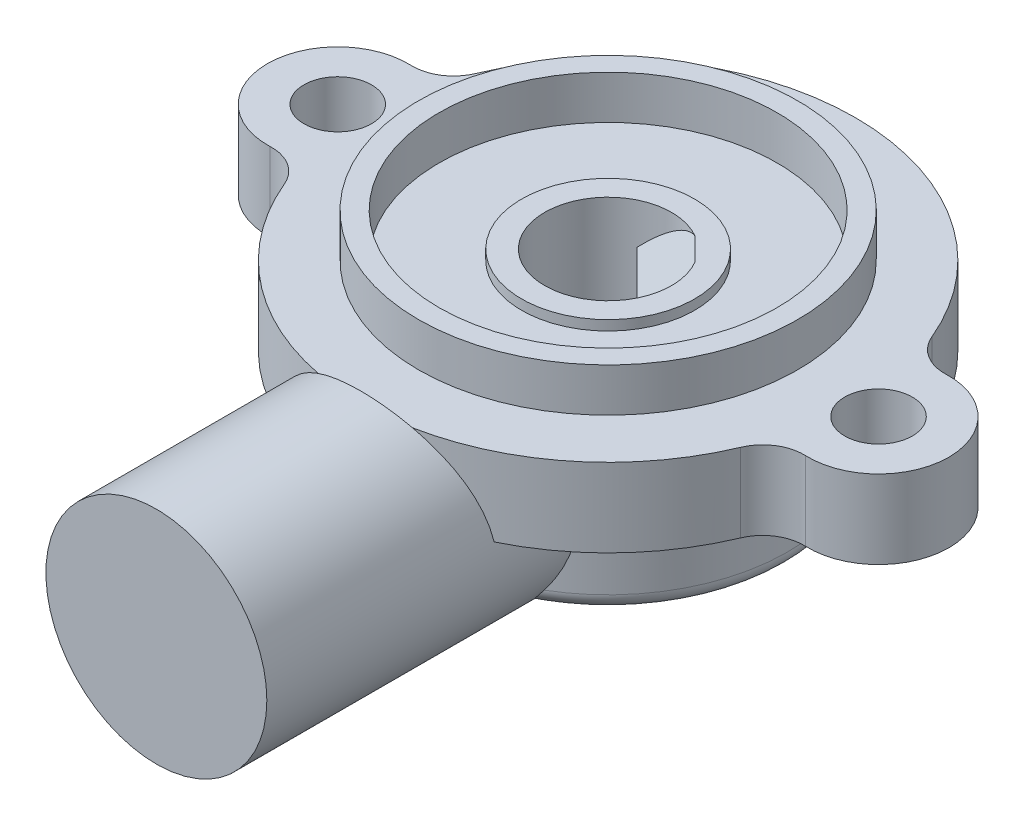
SolidWorks part; units mm, degrees
ref_plane "Front Plane" through (0, 0, 0) normal (0, 0, 1) x (1, 0, 0)
ref_plane "Top Plane" through (0, 0, 0) normal (0, 1, 0) x (1, 0, 0)
ref_plane "Right Plane" through (0, 0, 0) normal (1, 0, 0) x (0, 0, -1)
sketch "Sketch2" plane through (0, 0, 0) normal (0, 1, 0) x (1, 0, 0)
  line L0 (-20.828, 0) -> (20.828, 0) construction
  line L1 (-2.1716, 4.3808) -> (4.3808, -2.1716)
  line L2 (1.1046, 1.1046) -> (-3.4574, -3.4574) construction
  line L3 (-26.2509, 0) -> (-20.828, 0) construction
  line L4 (20.828, 0) -> (26.2509, 0) construction
  arc A0 (-18.4199, -4.8589) -> (18.4199, -4.8589) centre (0, 0) ccw
  circle A1 centre (-20.828, 0) radius 2.6035
  circle A2 centre (20.828, 0) radius 2.6035
  circle A3 centre (0, 0) radius 14.605
  circle A4 centre (0, 0) radius 13.0175
  circle A5 centre (0, 0) radius 6.6675
  circle A6 centre (0, 0) radius 4.8895
  arc A7 (-18.4199, 4.8589) -> (-18.4199, -4.8589) centre (-20.828, 0) ccw
  arc A8 (18.4199, -4.8589) -> (18.4199, 4.8589) centre (20.828, 0) ccw
  arc A9 (18.4199, 4.8589) -> (-18.4199, 4.8589) centre (0, 0) ccw
  point P15 (0, 0)
  dimension "D1" = 38.1
  dimension "D3" = 5.207
  dimension "D4" = 29.21
  dimension "D5" = 26.035
  dimension "D6" = 13.335
  dimension "D7" = 9.779
  dimension "D2" = 41.656
  dimension "D8" = 6.4516
  dimension "D9" = 52.5018
  dimension "D10" = 45
sketch "Sketch3" plane through (0, 0, 0) normal (0, 1, 0) x (1, 0, 0)
  circle A0 centre (-20.828, 0) radius 2.6035 construction
  circle A1 centre (20.828, 0) radius 2.6035 construction
  arc A2 (18.4199, -4.8589) -> (18.4199, 4.8589) centre (20.828, 0) ccw construction
  arc A3 (-18.4199, -4.8589) -> (18.4199, -4.8589) centre (0, 0) ccw construction
  arc A4 (18.4199, 4.8589) -> (-18.4199, 4.8589) centre (0, 0) ccw construction
  arc A5 (-18.4199, 4.8589) -> (-18.4199, -4.8589) centre (-20.828, 0) ccw construction
  circle A6 centre (-20.828, 0) radius 2.6035
  circle A7 centre (20.828, 0) radius 2.6035
  arc A8 (18.4199, -4.8589) -> (18.4199, 4.8589) centre (20.828, 0) ccw
  arc A9 (-18.4199, -4.8589) -> (18.4199, -4.8589) centre (0, 0) ccw
  arc A10 (18.4199, 4.8589) -> (-18.4199, 4.8589) centre (0, 0) ccw
  arc A11 (-18.4199, 4.8589) -> (-18.4199, -4.8589) centre (-20.828, 0) ccw
extrude "Boss-Extrude1" add sketch "Sketch3" along normal blind 9.398
sketch "Sketch4" plane through (0, 9.398, 0) normal (0, 1, 0) x (1, 0, 0)
  circle A0 centre (0, 0) radius 13.0175 construction
  circle A1 centre (0, 0) radius 13.0175
  circle A2 centre (0, 0) radius 14.605 construction
  circle A3 centre (0, 0) radius 14.605
  arc A8 (-18.4199, -4.8589) -> (18.4199, -4.8589) centre (0, 0) ccw
  arc A9 (18.4199, -4.8589) -> (18.4199, 4.8589) centre (20.828, 0) ccw
  arc A10 (18.4199, 4.8589) -> (-18.4199, 4.8589) centre (0, 0) ccw
  arc A11 (-18.4199, 4.8589) -> (-18.4199, -4.8589) centre (-20.828, 0) ccw
  arc A12 (-18.4199, -4.8589) -> (18.4199, -4.8589) centre (0, 0) ccw
  arc A13 (18.4199, -4.8589) -> (18.4199, 4.8589) centre (20.828, 0) ccw
  arc A14 (18.4199, 4.8589) -> (-18.4199, 4.8589) centre (0, 0) ccw
  arc A15 (-18.4199, 4.8589) -> (-18.4199, -4.8589) centre (-20.828, 0) ccw
  circle M7 centre (-20.828, 0) radius 2.6035
  arc M8 (-18.4199, -4.8589) -> (18.4199, -4.8589) centre (0, 0) ccw
  arc M9 (18.4199, -4.8589) -> (18.4199, 4.8589) centre (20.828, 0) ccw
  arc M10 (18.4199, 4.8589) -> (-18.4199, 4.8589) centre (0, 0) ccw
  arc M11 (-18.4199, 4.8589) -> (-18.4199, -4.8589) centre (-20.828, 0) ccw
  circle M12 centre (20.828, 0) radius 2.6035
  dimension "D1" = 0
extrude "Cut-Extrude1" cut sketch "Sketch4" against normal blind 3.3528 contours A3 M11 M8 M9 M10 M12 M7 | A1 region at (0, 9.398, 0) region at (-25.6022, 9.398, 0)
sketch "Sketch5" plane through (0, 0, 0) normal (0, -1, 0) x (1, 0, 0)
  line L0 (-20.828, 0) -> (20.828, 0) construction
  circle A0 centre (0, 0) radius 13.843
  dimension "D1" = 27.686
extrude "Boss-Extrude2" add sketch "Sketch5" along normal blind 7.747
sketch "Sketch6" plane through (0, -7.747, 0) normal (0, -1, 0) x (1, 0, 0)
  line L0 (-20.828, 0) -> (20.828, 0) construction
  circle A0 centre (0, 0) radius 8.4455
  dimension "D1" = 16.891
extrude "Boss-Extrude3" add sketch "Sketch6" along normal blind 1.905
sketch "Sketch7" plane through (0, 0, 0) normal (0, 0, 1) x (1, 0, 0)
  line L0 (-13.843, -7.747) -> (13.843, -7.747) construction
  line L1 (0, -1.651) -> (0, 0) construction
  circle A0 centre (0, -1.651) radius 8.509
  dimension "D1" = 17.018
  dimension "D2" = 6.096
extrude "Boss-Extrude4" add sketch "Sketch7" along normal blind 34.798
sketch "Sketch8" plane through (0, 6.0452, 0) normal (0, 1, 0) x (1, 0, 0)
  line L0 (3.6293, -14.1469) -> (3.6293, -18.7011) construction
  line L1 (-3.6293, -18.7011) -> (-3.6293, -14.1469) construction
  line L2 (3.6293, -14.1469) -> (3.6293, -18.7011)
  line L3 (3.6293, -12.5013) -> (3.6293, 0)
  line L4 (3.6293, 0) -> (-3.6293, 0)
  line L5 (-3.6293, 0) -> (-3.6293, -12.5013)
  line L6 (3.6293, -12.5013) -> (3.6293, 0)
  line L7 (3.6293, 0) -> (-3.6293, 0)
  line L8 (-3.6293, 0) -> (-3.6293, -12.5013)
  line L9 (-3.6293, -18.7011) -> (-3.6293, -14.1469)
  circle A0 centre (0, 0) radius 14.605 construction
  circle A1 centre (0, 0) radius 13.0175 construction
  arc A2 (-3.6293, -14.1469) -> (3.6293, -14.1469) centre (0, 0) ccw
  arc A3 (-3.6293, -12.5013) -> (3.6293, -12.5013) centre (0, 0) ccw
  arc A4 (-18.4199, -4.8589) -> (18.4199, -4.8589) centre (0, 0) ccw construction
  arc A5 (-3.6293, -12.5013) -> (3.6293, -12.5013) centre (0, 0) ccw
  arc A6 (-3.6293, -12.5013) -> (3.6293, -12.5013) centre (0, 0) ccw
  arc A7 (-3.6293, -18.7011) -> (3.6293, -18.7011) centre (0, 0) ccw
  line M9 (3.6293, -14.1469) -> (3.6293, -18.7011)
  line M15 (-3.6293, -18.7011) -> (-3.6293, -14.1469)
  dimension "D1" = 0
extrude "Cut-Extrude2" cut sketch "Sketch8" along normal through all contours L8 A3 L6 L7 | A7 A2 M15 M9 region at (0, 6.0452, 16.6928) region at (0, 6.0452, 6.4243)
fillet "Fillet1" radius 3.175 4 edges at (18.4199, 3.0226, -4.8589) (18.4199, 3.0226, 4.8589) (-18.4199, 3.0226, -4.8589) (-18.4199, 3.0226, 4.8589)
chamfer "Chamfer1" distance 1.905 angle 45 1 edges at (0, -9.652, -8.4455)
sketch "Sketch9" plane through (0, 6.0452, 0) normal (0, 1, 0) x (1, 0, 0)
  circle A0 centre (0, 0) radius 6.6675 construction
  circle A1 centre (0, 0) radius 6.6675
extrude "Boss-Extrude5" add sketch "Sketch9" along normal blind 0.762
sketch "Sketch10" plane through (0, 6.8072, 0) normal (0, 1, 0) x (1, 0, 0)
  line L0 (-2.1716, 4.3808) -> (4.3808, -2.1716) construction
  line L1 (-2.1716, 4.3808) -> (4.3808, -2.1716)
  circle A0 centre (0, 0) radius 4.8895 construction
  arc A1 (-2.1716, 4.3808) -> (4.3808, -2.1716) centre (0, 0) ccw
extrude "Cut-Extrude3" cut sketch "Sketch10" against normal blind 11.43
chamfer "Chamfer2" distance 3.175 angle 45 1 edges at (1.1046, 6.8072, -1.1046)
fillet "Fillet2" radius 1.27 1 edges at (0, -7.747, -13.843)
